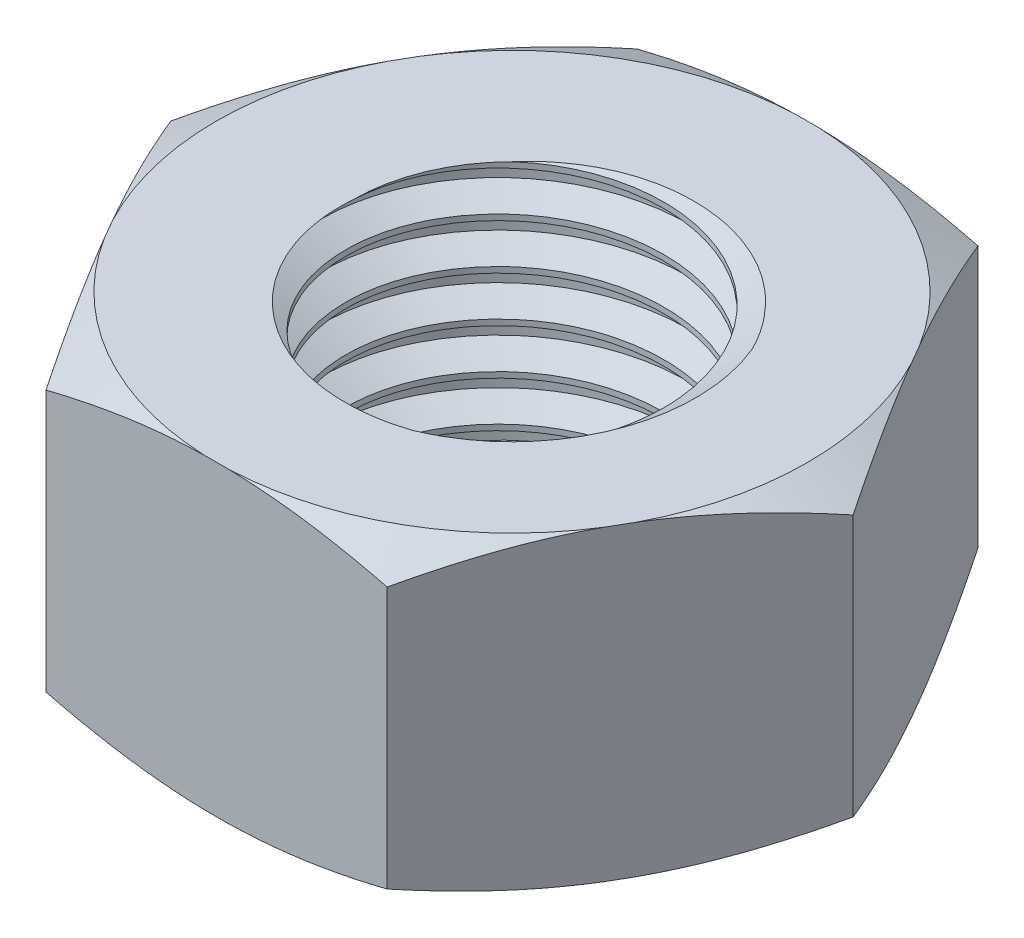
SolidWorks part; units mm, degrees
ref_plane "Front Plane" through (0, 0, 0) normal (0, 0, 1) x (1, 0, 0)
ref_plane "Top Plane" through (0, 0, 0) normal (0, 1, 0) x (1, 0, 0)
ref_plane "Right Plane" through (0, 0, 0) normal (1, 0, 0) x (0, 0, -1)
sketch "Sketch1" plane through (0, 0, 0) normal (1, 0, 0) x (0, 0, -1)
  line L0 (0, 0) -> (0, 6.75) construction
  line L1 (-3.5, 0) -> (-3.5, 6.75)
  line L2 (-3.5, 6.75) -> (-6.5, 6.75)
  line L6 (-6.5, 0) -> (-3.5, 0)
  line L7 (-7.5, 6.25) -> (-7.5, 0.5)
  line L8 (-7.5, 0.5) -> (-6.5, 0)
  line L9 (-6.5, 6.75) -> (-7.5, 6.25)
  point P6 (-7.5, 6.75)
  point P8 (-7.5, 0)
  dimension "D1" = 6.75
  dimension "D2" = 3.5
  dimension "D3" = 4
  dimension "D4" = 0.5
  dimension "D5" = 1
  dimension "D6" = 1
  dimension "D7" = 0.5
revolve "Revolve1" add sketch "Sketch1" angle 360 about L0
sketch "Sketch2" plane through (0, 6.75, 0) normal (0, 1, 0) x (1, 0, 0)
  line L1 (-3.75, 6.4952) -> (-7.5, 0)
  line L2 (-7.5, 0) -> (-3.75, -6.4952)
  line L3 (-3.75, -6.4952) -> (3.75, -6.4952)
  line L4 (3.75, -6.4952) -> (7.5, 0)
  line L5 (7.5, 0) -> (3.75, 6.4952)
  line L6 (3.75, 6.4952) -> (-3.75, 6.4952)
  circle A0 centre (0, 0) radius 6.4952 construction
  circle A1 centre (0, 0) radius 7.5 construction
  point P1 (0, 0)
extrude "Cut-Extrude1" cut sketch "Sketch2" against normal through all and the other way through all flip side to cut
thread "Thread1" pitch 1 method cut profile "Thread Profile1" start angle 0, offset 1, length 0, pitch 1, diameter 7
ref_plane "Plane1" through (-3.5, 7.75, 0) normal (0, 0, -1) x (1, 0, 0)
sketch "Thread Profile1" plane through (-3.5, 7.75, 0) normal (0, 0, -1) x (1, 0, 0)
  line L0 (0, 0) -> (0, 1) construction
  line L11 (0, 0) -> (0, 0.875)
  line L12 (0, 0.875) -> (-0.5413, 0.5625)
  line L13 (-0.5413, 0.5625) -> (-0.5413, 0.3125)
  line L15 (-0.5413, 0.3125) -> (0, 0)
  line L17 (-0.5413, 0.4375) -> (0, 0.4375) construction
  point P2 (0, 0)
  dimension "Pitch" = 1
  dimension "Profile_Angle" = 60
  dimension "Profile_Land" = 0.25
  dimension "Profile_Height" = 0.5413
